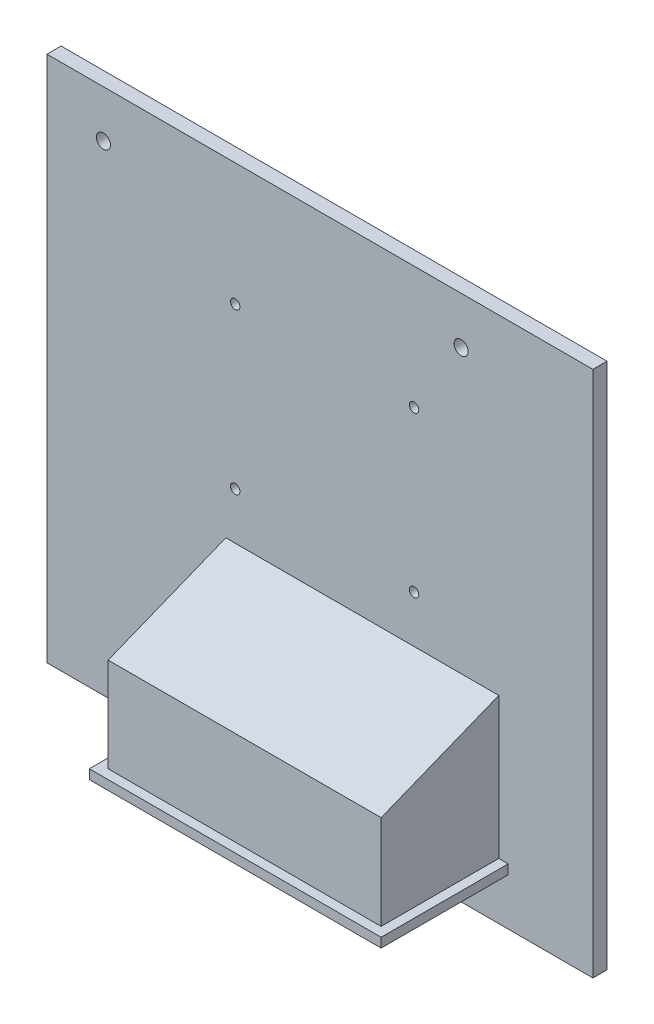
SolidWorks part; units mm, degrees
ref_plane "Front" through (0, 0, 0) normal (0, 0, 1) x (1, 0, 0)
ref_plane "Top" through (0, 0, 0) normal (0, 1, 0) x (1, 0, 0)
ref_plane "Right" through (0, 0, 0) normal (1, 0, 0) x (0, 0, -1)
sketch "Sketch1" plane through (0, 0, 0) normal (0, 0, 1) x (1, 0, 0)
  line L1 (-58, -56) -> (58, -56)
  line L2 (-58, -56) -> (-58, 56)
  line L3 (-58, 56) -> (58, 56)
  line L4 (58, -56) -> (58, 56)
  line L5 (-58, -56) -> (58, 56) construction
  line L6 (-58, 56) -> (58, -56) construction
  point P0 (0, 0)
  dimension "D1" = 112
  dimension "D2" = 116
extrude "Boss-Extrude1" add sketch "Sketch1" along normal blind 3
sketch "Sketch2" plane through (0, 0, 3) normal (0, 0, 1) x (1, 0, 0)
  line L0 (-58, -56) -> (58, -56) construction
  line L1 (-20, -48) -> (38, -48)
  line L2 (-20, -48) -> (-20, -14)
  line L3 (-20, -14) -> (38, -14)
  line L4 (38, -48) -> (38, -14)
  line L5 (-20, -48) -> (38, -14) construction
  line L6 (-20, -14) -> (38, -48) construction
  line L7 (58, -56) -> (58, 56) construction
  point P0 (9, -31)
  dimension "D1" = 34
  dimension "D2" = 58
  dimension "D3" = 8
  dimension "D4" = 20
extrude "Boss-Extrude2" add sketch "Sketch2" along normal blind 25
chamfer "Chamfer1" distance 25 distance2 10 1 edges at (9, -14, 28) first distance on face at (9, -14, 15.5)
ref_plane "Plane1" through (0, -43, 0) normal (0, -1, 0) x (-1, 0, 0)
ref_plane "Plane2" through (0, -46, 0) normal (0, -1, 0) x (-1, 0, 0)
sketch "Sketch4" plane through (0, -46, 0) normal (0, -1, 0) x (-1, 0, 0)
  line L4 (20, -3) -> (-38, -3)
  line L5 (-38, -3) -> (-38, -28)
  line L6 (-38, -28) -> (20, -28)
  line L7 (20, -28) -> (20, -3)
  line L8 (22, -3) -> (-40, -3)
  line L9 (-38, -3) -> (-38, -28)
  line L10 (-38, -28) -> (20, -28)
  line L11 (20, -28) -> (20, -3)
  line L16 (22, -1) -> (-40, -1)
  line L17 (-40, -1) -> (-40, -30)
  line L18 (-40, -30) -> (22, -30)
  line L19 (22, -30) -> (22, -1)
  line L20 (22, -1) -> (-40, -1)
  line L21 (-40, -1) -> (-40, -30)
  line L22 (-40, -30) -> (22, -30)
  line L23 (22, -30) -> (22, -1)
  dimension "D1" = 0
  dimension "D2" = 2
extrude "Boss-Extrude4" add sketch "Sketch4" against normal blind 2 contours L22 L23 L8 L11 L10 L9 L21 region at (-21, -46, 3.6762)
sketch "Sketch5" plane through (0, 0, 3) normal (0, 0, 1) x (1, 0, 0)
  line L0 (58, 56) -> (-58, 56) construction
  line L1 (-58, 56) -> (-58, -56) construction
  line L2 (58, -56) -> (58, 56) construction
  line L3 (-58, -56) -> (58, -56) construction
  circle A0 centre (-46, 46) radius 1.5
  circle A1 centre (30, 46) radius 1.5
  circle A2 centre (-36, -46) radius 1.5
  dimension "D1" = 3
  dimension "D2" = 3
  dimension "D3" = 3
  dimension "D6" = 28
  dimension "D8" = 22
  dimension "D4" = 10
  dimension "D5" = 12
  dimension "D7" = 10
extrude "Cut-Extrude1" cut sketch "Sketch5" against normal up to next
sketch "Sketch6" plane through (0, 0, 3) normal (0, 0, 1) x (1, 0, 0)
  line L0 (-20, -14) -> (-20, -44) construction
  line L1 (-20, 32) -> (22, 32)
  line L2 (-20, 32) -> (-20, 28)
  line L3 (-20, 28) -> (22, 28)
  line L4 (22, 32) -> (22, 28)
  line L5 (-20, 32) -> (22, 28) construction
  line L6 (-20, 28) -> (22, 32) construction
  line L7 (-20, -2) -> (22, -2)
  line L8 (-20, -2) -> (-20, -6)
  line L9 (-20, -6) -> (22, -6)
  line L10 (22, -2) -> (22, -6)
  line L11 (-20, -2) -> (22, -6) construction
  line L12 (-20, -6) -> (22, -2) construction
  line L13 (-16, 28) -> (-12, 28)
  line L14 (-16, 28) -> (-16, -2)
  line L15 (-16, -2) -> (-12, -2)
  line L16 (-12, 28) -> (-12, -2)
  line L17 (-16, 28) -> (-12, -2) construction
  line L18 (-16, -2) -> (-12, 28) construction
  line L19 (14, 28) -> (18, 28)
  line L20 (14, 28) -> (14, -2)
  line L21 (14, -2) -> (18, -2)
  line L22 (18, 28) -> (18, -2)
  line L23 (14, 28) -> (18, -2) construction
  line L24 (14, -2) -> (18, 28) construction
  line L25 (38, -14) -> (-20, -14) construction
  circle A0 centre (-18, 30) radius 1
  circle A1 centre (20, 30) radius 1
  circle A2 centre (20, -4) radius 1
  circle A3 centre (-18, -4) radius 1
  point P0 (1, 30)
  point P5 (1, -4)
  point P15 (-14, 13)
  point P19 (16, 13)
  point P28 (0, 0)
  point P29 (0, 0)
  point P30 (0, 0)
  point P31 (0, 0)
  point P32 (27.467, 35.0226)
  point P33 (-14.0461, 15.2572)
  point P38 (0, 0)
  point P39 (0, 0)
  dimension "D8" = 2
  dimension "D10" = 2
  dimension "D11" = 2
  dimension "D12" = 2
  dimension "D13" = 2
  dimension "D14" = 2
  dimension "D1" = 4
  dimension "D2" = 42
  dimension "D3" = 4
  dimension "D4" = 42
  dimension "D5" = 30
  dimension "D6" = 4
  dimension "D7" = 4
  dimension "D9" = 2
  dimension "D15" = 2
  dimension "D16" = 4
  dimension "D17" = 4
  dimension "D18" = 2
  dimension "D19" = 10
extrude "Cut-Extrude2" cut sketch "Sketch6" against normal up to next contours A0 | A1 | A3 | A2 region at (-18, 30, 3) region at (20, 30, 3) region at (20, -4, 3) region at (-18, -4, 3)
